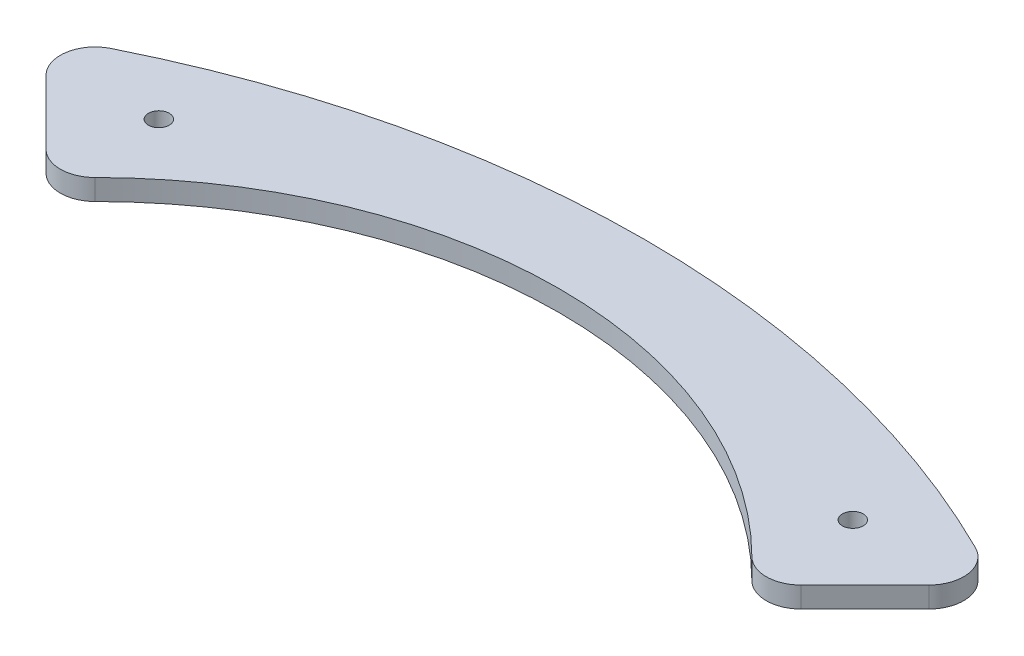
SolidWorks part; units mm, degrees
material "1060 Alloy"
ref_plane "Front Plane" through (0, 0, 0) normal (0, 0, 1) x (1, 0, 0)
ref_plane "Top Plane" through (0, 0, 0) normal (0, 1, 0) x (1, 0, 0)
ref_plane "Right Plane" through (0, 0, 0) normal (1, 0, 0) x (0, 0, -1)
sketch "Sketch1" plane through (0, 0, 0) normal (0, 1, 0) x (1, 0, 0)
  line L0 (-68.4085, 122.1486) -> (-50.7308, 104.4709)
  line L1 (68.4085, 122.1486) -> (50.7308, 104.4709)
  line L3 (0, 0) -> (-117.9329, 117.9329) construction
  line L4 (0, 0) -> (118.2874, 118.2874) construction
  line L5 (0, 0) -> (0, 174.1104) construction
  line L6 (-15, 127.1181) -> (15, 127.1181) construction
  line L7 (-15, 127.1181) -> (-15, 116.1181) construction
  line L8 (-15, 116.1181) -> (15, 116.1181) construction
  line L9 (15, 127.1181) -> (15, 116.1181) construction
  arc A0 (-68.4085, 122.1486) -> (68.4085, 122.1486) centre (0, 0) cw
  arc A1 (-50.7308, 104.4709) -> (50.7308, 104.4709) centre (0, 60.7058) cw
  circle A2 centre (0, 0) radius 128 construction
  dimension "D1" = 140
  dimension "D6" = 67
  dimension "D7" = 12
  dimension "D2" = 25
  dimension "D3" = 45
  dimension "D4" = 38
  dimension "D5" = 38
  dimension "D8" = 11
  dimension "D9" = 30
extrude "Boss-Extrude1" add sketch "Sketch1" along normal blind 3
fillet "Fillet1" radius 5 4 edges at (68.4085, 1.5, -122.1486) (50.7308, 1.5, -104.4709) (-68.4085, 1.5, -122.1486) (-50.7308, 1.5, -104.4709)
sketch "Sketch2" plane through (0, 3, 0) normal (0, 1, 0) x (1, 0, 0)
  circle A0 centre (-50, 120) radius 1.5
  circle A1 centre (50, 120) radius 1.5
  dimension "D1" = 3
  dimension "D2" = 120
  dimension "D3" = 50
  dimension "D4" = 50
extrude "Cut-Extrude1" cut sketch "Sketch2" against normal up to next
